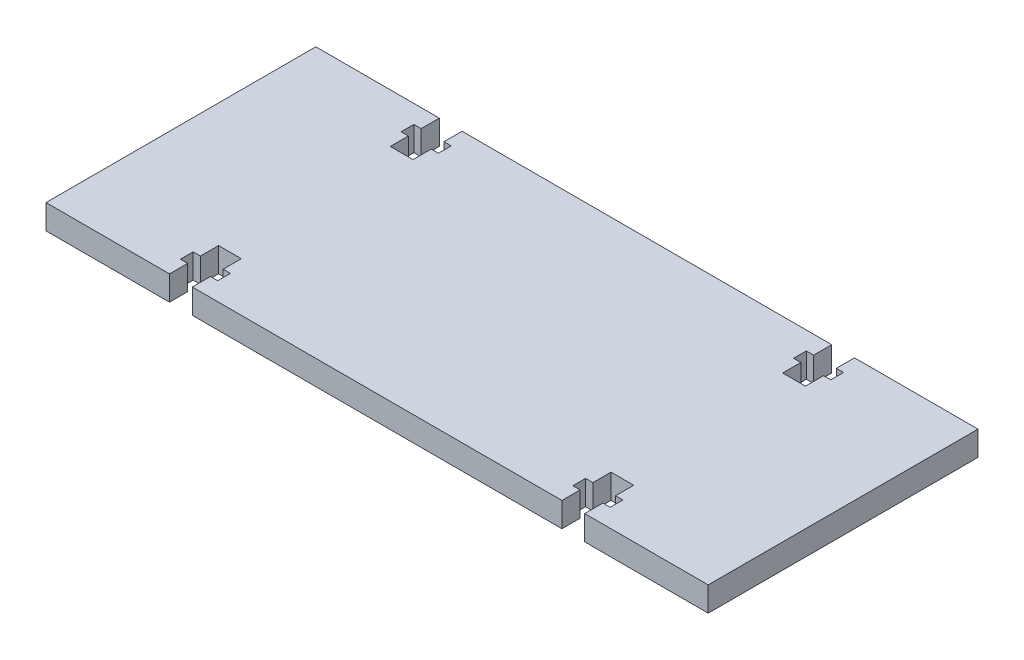
SolidWorks part; units mm, degrees
ref_plane "Front Plane" through (0, 0, 0) normal (0, 0, 1) x (1, 0, 0)
ref_plane "Top Plane" through (0, 0, 0) normal (0, 1, 0) x (1, 0, 0)
ref_plane "Right Plane" through (0, 0, 0) normal (1, 0, 0) x (0, 0, -1)
sketch "Sketch1" plane through (0, 0, 0) normal (0, 1, 0) x (1, 0, 0)
  line L1 (-42.8625, -17.4625) -> (42.8625, -17.4625)
  line L2 (-42.8625, -17.4625) -> (-42.8625, 17.4625)
  line L3 (-42.8625, 17.4625) -> (42.8625, 17.4625)
  line L4 (42.8625, -17.4625) -> (42.8625, 17.4625)
  line L5 (-42.8625, -17.4625) -> (42.8625, 17.4625) construction
  line L6 (-42.8625, 17.4625) -> (42.8625, -17.4625) construction
  point P0 (0, 0)
  dimension "D1" = 85.725
  dimension "D2" = 34.925
extrude "Boss-Extrude1" add sketch "Sketch1" along normal blind 3.175
sketch "Sketch3" plane through (0, 0, 0) normal (0, -1, 0) x (1, 0, 0)
  line L0 (-42.8625, 17.4625) -> (42.8625, 17.4625) construction
  line L1 (-26.8732, 17.4625) -> (-23.9268, 17.4625)
  line L2 (-26.8732, 17.4625) -> (-26.8732, 15.113)
  line L3 (-26.8732, 11.1125) -> (-23.9268, 11.1125)
  line L4 (-23.9268, 17.4625) -> (-23.9268, 15.113)
  line L5 (-26.8732, 17.4625) -> (-23.9268, 11.1125) construction
  line L6 (-26.8732, 15.113) -> (-27.813, 15.113)
  line L7 (-22.987, 13.462) -> (-23.9268, 13.462)
  line L8 (-22.987, 13.462) -> (-22.987, 15.113)
  line L9 (-22.987, 15.113) -> (-23.9268, 15.113)
  line L10 (-27.813, 13.462) -> (-27.813, 15.113)
  line L11 (-22.987, 13.462) -> (-27.813, 15.113) construction
  line L12 (-22.987, 15.113) -> (-27.813, 13.462) construction
  line L13 (-23.9268, 13.462) -> (-23.9268, 11.1125)
  line L14 (-26.8732, 13.462) -> (-27.813, 13.462)
  line L15 (-26.8732, 13.462) -> (-26.8732, 11.1125)
  line L16 (-25.4, 11.1125) -> (-25.4, 17.4625) construction
  line L17 (0, 17.4625) -> (0, -17.4625) construction
  line L18 (42.8625, -17.4625) -> (-42.8625, -17.4625) construction
  line L19 (25.4, 11.1125) -> (25.4, 17.4625) construction
  line L20 (22.987, 15.113) -> (27.813, 13.462) construction
  line L21 (22.987, 13.462) -> (27.813, 15.113) construction
  line L22 (26.8732, 17.4625) -> (23.9268, 11.1125) construction
  line L23 (26.8732, 13.462) -> (26.8732, 11.1125)
  line L24 (26.8732, 13.462) -> (27.813, 13.462)
  line L25 (23.9268, 13.462) -> (23.9268, 11.1125)
  line L26 (27.813, 13.462) -> (27.813, 15.113)
  line L27 (22.987, 15.113) -> (23.9268, 15.113)
  line L28 (22.987, 13.462) -> (22.987, 15.113)
  line L29 (22.987, 13.462) -> (23.9268, 13.462)
  line L30 (26.8732, 15.113) -> (27.813, 15.113)
  line L31 (23.9268, 17.4625) -> (23.9268, 15.113)
  line L32 (26.8732, 11.1125) -> (23.9268, 11.1125)
  line L33 (26.8732, 17.4625) -> (26.8732, 15.113)
  line L34 (26.8732, 17.4625) -> (23.9268, 17.4625)
  line L35 (-42.8625, 0) -> (-37.7203, 0) construction
  line L36 (-42.8625, -17.4625) -> (-42.8625, 17.4625) construction
  line L37 (26.8732, -17.4625) -> (23.9268, -11.1125) construction
  line L38 (22.987, -13.462) -> (27.813, -15.113) construction
  line L39 (22.987, -15.113) -> (27.813, -13.462) construction
  line L40 (25.4, -11.1125) -> (25.4, -17.4625) construction
  line L41 (26.8732, -17.4625) -> (23.9268, -17.4625)
  line L42 (26.8732, -17.4625) -> (26.8732, -15.113)
  line L43 (26.8732, -11.1125) -> (23.9268, -11.1125)
  line L44 (23.9268, -17.4625) -> (23.9268, -15.113)
  line L45 (26.8732, -15.113) -> (27.813, -15.113)
  line L46 (22.987, -13.462) -> (23.9268, -13.462)
  line L47 (22.987, -13.462) -> (22.987, -15.113)
  line L48 (22.987, -15.113) -> (23.9268, -15.113)
  line L49 (27.813, -13.462) -> (27.813, -15.113)
  line L50 (23.9268, -13.462) -> (23.9268, -11.1125)
  line L51 (26.8732, -13.462) -> (27.813, -13.462)
  line L52 (26.8732, -13.462) -> (26.8732, -11.1125)
  line L53 (-25.4, -11.1125) -> (-25.4, -17.4625) construction
  line L54 (-22.987, -15.113) -> (-27.813, -13.462) construction
  line L55 (-22.987, -13.462) -> (-27.813, -15.113) construction
  line L56 (-26.8732, -17.4625) -> (-23.9268, -11.1125) construction
  line L57 (-26.8732, -13.462) -> (-26.8732, -11.1125)
  line L58 (-26.8732, -13.462) -> (-27.813, -13.462)
  line L59 (-23.9268, -13.462) -> (-23.9268, -11.1125)
  line L60 (-27.813, -13.462) -> (-27.813, -15.113)
  line L61 (-22.987, -15.113) -> (-23.9268, -15.113)
  line L62 (-22.987, -13.462) -> (-22.987, -15.113)
  line L63 (-22.987, -13.462) -> (-23.9268, -13.462)
  line L64 (-26.8732, -15.113) -> (-27.813, -15.113)
  line L65 (-23.9268, -17.4625) -> (-23.9268, -15.113)
  line L66 (-26.8732, -11.1125) -> (-23.9268, -11.1125)
  line L67 (-26.8732, -17.4625) -> (-26.8732, -15.113)
  line L68 (-26.8732, -17.4625) -> (-23.9268, -17.4625)
  point P6 (-25.4, 14.2875)
  point P18 (-25.4, 14.2875)
  point P36 (25.4, 14.2875)
  point P56 (25.4, -14.2875)
  point P71 (-25.4, -14.2875)
  dimension "D1" = 6.35
  dimension "D2" = 2.9464
  dimension "D3" = 1.651
  dimension "D4" = 4.826
  dimension "D5" = 25.4
extrude "Cut-Extrude2" cut sketch "Sketch3" against normal through all
